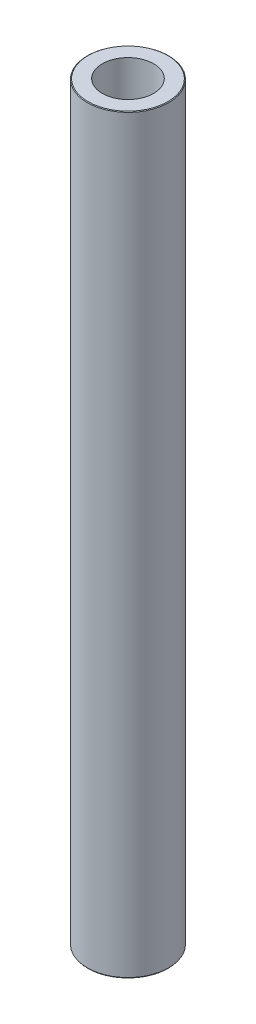
SolidWorks part; units mm, degrees
ref_plane "Front Plane" through (0, 0, 0) normal (0, 0, 1) x (1, 0, 0)
ref_plane "Top Plane" through (0, 0, 0) normal (0, 1, 0) x (1, 0, 0)
ref_plane "Right Plane" through (0, 0, 0) normal (1, 0, 0) x (0, 0, -1)
sketch "Sketch1" plane through (0, 0, 0) normal (0, 1, 0) x (1, 0, 0)
  circle A0 centre (0, 0) radius 32.5
  dimension "SHAFT_OD" = 65
extrude "Boss-Extrude1" add sketch "Sketch1" along normal blind 600
sketch "Sketch2" plane through (0, 0, 0) normal (0, 1, 0) x (1, 0, 0)
  circle A0 centre (0, 0) radius 20.5595
  dimension "BORE_D" = 41.119
extrude "Cut-Extrude1" cut sketch "Sketch2" along normal through all
chamfer "Chamfer1" distance 0.4321 angle 54.144 2 edges at (0, 600, 32.5) (0, 0, 32.5) first distance on face at (0, 600, 32.5) first distance on face at (0, 0, 20.5595)
